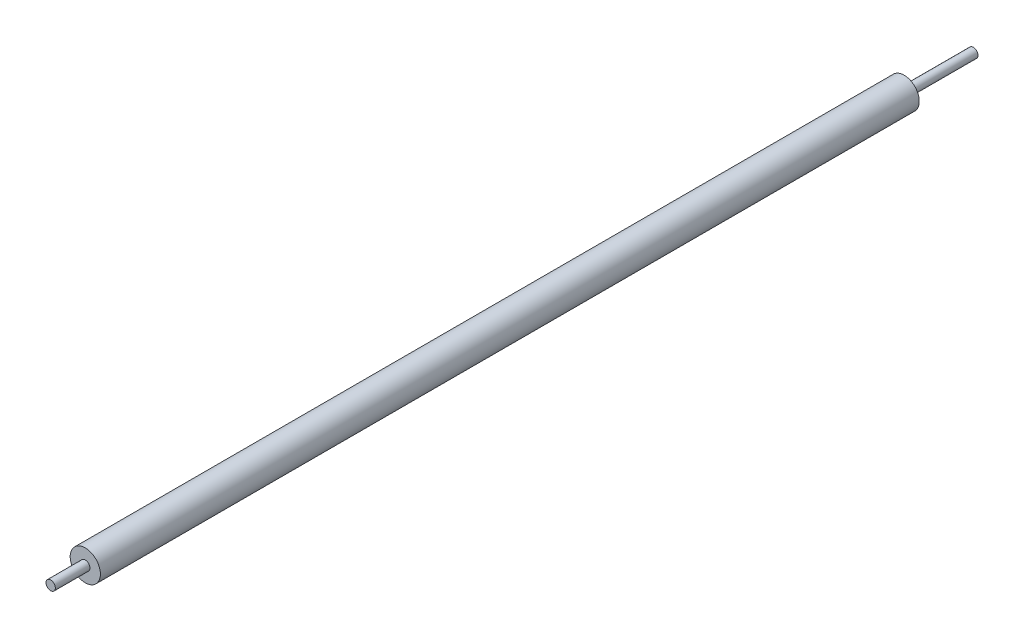
SolidWorks part; units mm, degrees
ref_plane "Front Plane" through (0, 0, 0) normal (0, 0, 1) x (1, 0, 0)
ref_plane "Top Plane" through (0, 0, 0) normal (0, 1, 0) x (1, 0, 0)
ref_plane "Right Plane" through (0, 0, 0) normal (1, 0, 0) x (0, 0, -1)
sketch "wire_sketch" plane through (0, 0, 0) normal (0, 0, 1) x (1, 0, 0)
  circle A0 centre (0, 0) radius 1.31
  circle A1 centre (0, 0) radius 0.4064
  dimension "D1" = 0.8128
  dimension "D2" = 2.62
extrude "copper" add sketch "wire_sketch" along normal blind 80 contours A1 region at (0, 0, 0)
extrude "insulation" add sketch "wire_sketch<3>" along normal offset from surface (71 mm away) 3 from offset 6 separate body up to face at (0.4064, 0, 80)
sketch "wire_sketch<3>" plane through (0, 0, 0) normal (0, 0, 1) x (1, 0, 0) same geometry as "wire_sketch"
